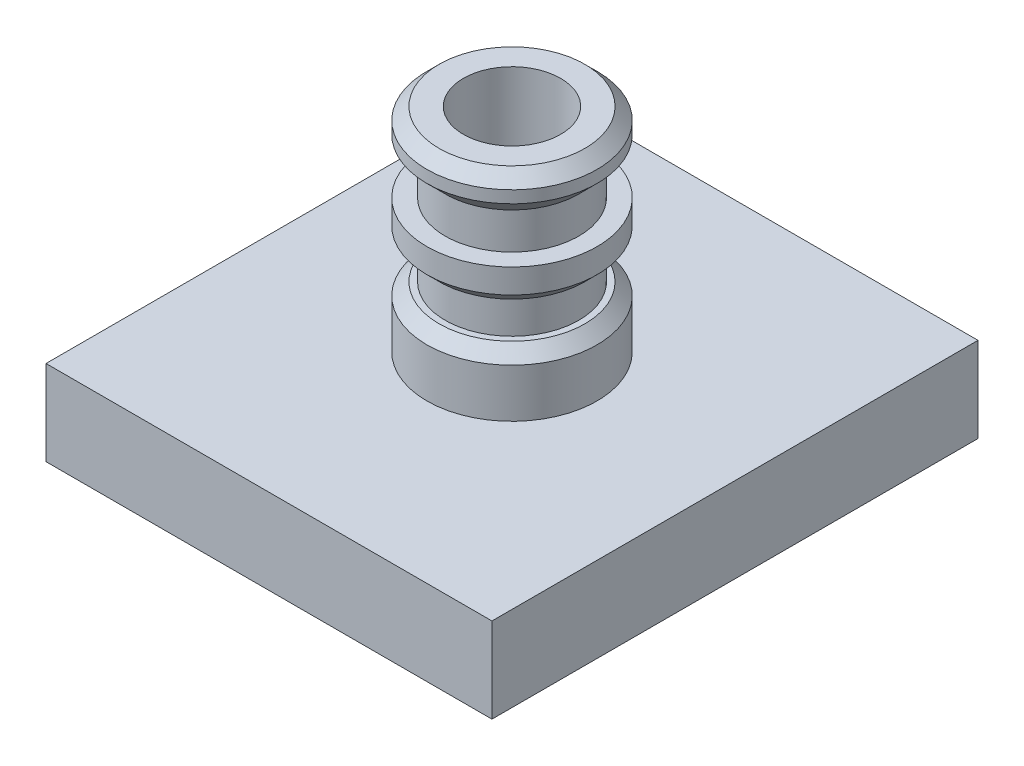
SolidWorks part; units mm, degrees
ref_plane "Alzado" through (0, 0, 0) normal (0, 0, 1) x (1, 0, 0)
ref_plane "Planta" through (0, 0, 0) normal (0, 1, 0) x (1, 0, 0)
ref_plane "Vista lateral" through (0, 0, 0) normal (1, 0, 0) x (0, 0, -1)
sketch "Croquis1" plane through (0, 0, 0) normal (0, 1, 0) x (1, 0, 0)
  line L1 (-18.35, -20) -> (18.35, -20)
  line L2 (-18.35, -20) -> (-18.35, 20)
  line L3 (-18.35, 20) -> (18.35, 20)
  line L4 (18.35, -20) -> (18.35, 20)
  line L5 (-18.35, -20) -> (18.35, 20) construction
  line L6 (-18.35, 20) -> (18.35, -20) construction
  circle A0 centre (0, 0) radius 4
  point P0 (0, 0)
  dimension "D3" = 8
  dimension "D1" = 36.7
  dimension "D2" = 40
extrude "Saliente-Extruir1" add sketch "Croquis1" along normal blind 7
sketch "Croquis2" plane through (0, 0, 0) normal (1, 0, 0) x (0, 0, -1)
  line L1 (4, 7) -> (0, 7) construction
  line L2 (0, 7) -> (0, 17.1204) construction
  line L3 (7, 7) -> (7, 12)
  line L4 (7, 12) -> (5.5, 12)
  line L5 (5.5, 12) -> (5.5, 15)
  line L6 (5.5, 15) -> (7, 15)
  line L7 (7, 15) -> (7, 18)
  line L8 (7, 18) -> (5.5, 18)
  line L9 (5.5, 18) -> (5.5, 21)
  line L10 (5.5, 21) -> (7, 22.5)
  line L11 (7, 22.5) -> (7, 24.5)
  line L12 (20, 7) -> (-20, 7) construction
  line L13 (4, 7) -> (4, 24.5)
  line L14 (4, 7) -> (-4, 7) construction
  line L15 (4, 7) -> (-4, 7) construction
  line L16 (7, 24.5) -> (4, 24.5)
  line L17 (4, 7) -> (7, 7)
  dimension "D1" = 5
  dimension "D2" = 3
  dimension "D3" = 3
  dimension "D4" = 3
  dimension "D5" = 1.5
  dimension "D6" = 7
  dimension "D7" = 5.5
  dimension "D8" = 2
revolve "Revolución1" add sketch "Croquis2" angle 360 about L2
chamfer "Chaflán1" distance 1 angle 45 2 edges at (0, 12, -7) (0, 15, -7)
sketch "Croquis3" plane through (0, 0, 0) normal (0, -1, 0) x (1, 0, 0)
  circle A0 centre (0, 0) radius 6.55
  dimension "D1" = 13.1
extrude "Cortar-Extruir1" cut sketch "Croquis3" against normal blind 2
chamfer "Chaflán2" distance 1 angle 45 1 edges at (0, 24.5, -7)
